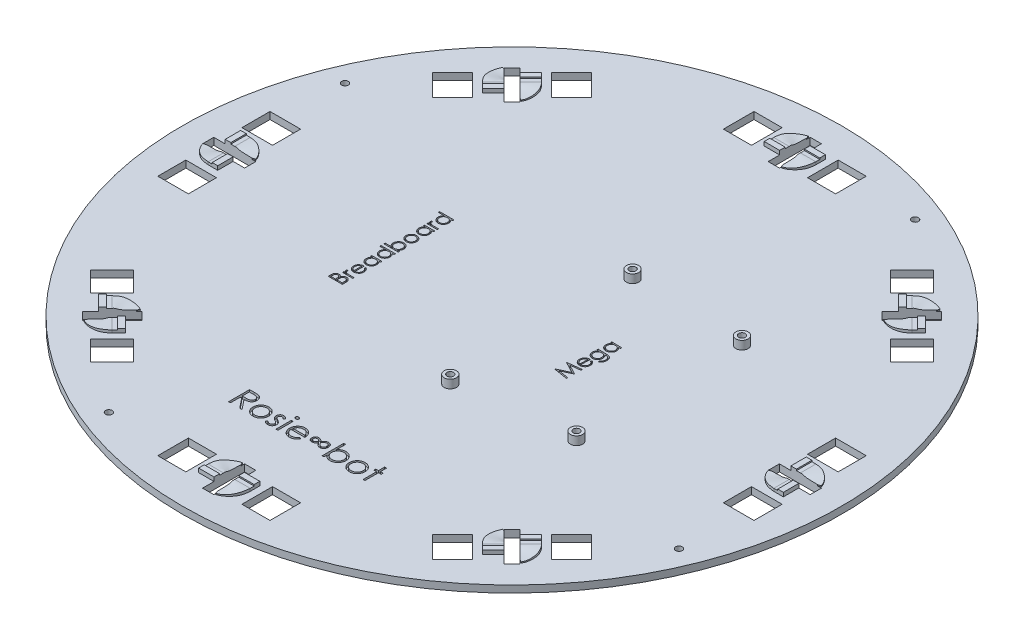
SolidWorks part; units mm, degrees
ref_plane "Front" through (0, 0, 0) normal (0, 0, 1) x (1, 0, 0)
ref_plane "Top" through (0, 0, 0) normal (0, 1, 0) x (1, 0, 0)
ref_plane "Right" through (0, 0, 0) normal (1, 0, 0) x (0, 0, -1)
sketch "Sketch1" plane through (0, 0, 0) normal (0, 1, 0) x (1, 0, 0)
  circle A0 centre (0, 0) radius 149.225
  dimension "D1" = 298.45
extrude "Boss-Extrude1" add sketch "Sketch1" along normal blind 3.175 contours A0
sketch "Sketch2" plane through (0, 3.175, 0) normal (0, 1, 0) x (1, 0, 0)
  line L1 (-2.54, -137.5833) -> (2.54, -137.5833)
  line L2 (-2.54, -137.5833) -> (-2.54, -118.5333)
  line L3 (-2.54, -118.5333) -> (2.54, -118.5333)
  line L4 (2.54, -137.5833) -> (2.54, -118.5333)
  circle A0 centre (0, 0) radius 149.225 construction
  point P4 (0, -118.5333)
  dimension "D1" = 5.08
  dimension "D2" = 19.05
  dimension "D3" = 137.5833
extrude "Cut-Extrude1" cut sketch "Sketch2" against normal up to next and the other way through all contours L1 L4 L3 L2
sketch "Sketch4" plane through (0, 3.175, 0) normal (0, 1, 0) x (1, 0, 0)
  line L0 (0, -128.0583) -> (-2.9434, -118.9995) construction
  line L1 (-2.9434, -118.9995) -> (0, -128.0583) construction
  line L2 (0, -128.0583) -> (-5.5987, -120.3525) construction
  line L3 (0, -128.0583) -> (-7.7059, -122.4597) construction
  line L4 (0, -128.0583) -> (-9.0588, -125.115) construction
  line L5 (0, -128.0583) -> (-9.525, -128.0583) construction
  line L9 (2.54, -118.5333) -> (-2.54, -118.5333) construction
  line L10 (2.54, -118.5333) -> (2.54, -137.5833) construction
  line L11 (-2.54, -118.5333) -> (-2.54, -137.5833) construction
  line L12 (2.54, -137.5833) -> (-2.54, -137.5833) construction
  circle A0 centre (0, -128.0583) radius 9.525 construction
  point P16 (0, -118.5333)
  point P19 (2.54, -128.0583)
  dimension "D1" = 18
  dimension "D2" = 18
  dimension "D3" = 18
  dimension "D4" = 18
  dimension "D5" = 18
ref_plane "Plane1" through (-37.6354, 0, 12.2285) normal (0.9511, 0, -0.309) x (-0.309, 0, -0.9511)
ref_plane "Plane2" through (-60.8954, 0, 44.2431) normal (0.809, 0, -0.5878) x (-0.5878, 0, -0.809)
ref_plane "Plane3" through (-60.8954, 0, 83.8153) normal (0.5878, 0, -0.809) x (-0.809, 0, -0.5878)
ref_plane "Plane4" through (-37.6354, 0, 115.8299) normal (0.309, 0, -0.9511) x (-0.9511, 0, -0.309)
ref_plane "Plane5" through (0, 0, 128.0583) normal (0, 0, -1) x (-1, 0, 0)
sketch "Sketch5" plane through (-37.6354, 0, 12.2285) normal (0.9511, 0, -0.309) x (-0.309, 0, -0.9511)
  line L0 (-111.947, 3.175) -> (-130.0646, 3.175) construction
  line L1 (-113.5711, 3.175) -> (-112.2657, 3.175)
  line L2 (-113.5711, 3.175) -> (-113.5711, 3.683)
  line L3 (-113.5711, 3.683) -> (-112.2657, 3.683)
  line L4 (-112.2657, 3.175) -> (-112.2657, 3.683)
  dimension "D2" = 0.508
sketch "Sketch6" plane through (-60.8954, 0, 44.2431) normal (0.809, 0, -0.5878) x (-0.5878, 0, -0.809)
  line L0 (-94.4025, 3.175) -> (-109.8143, 3.175) construction
  line L1 (-99.2801, 3.175) -> (-94.0764, 3.175)
  line L2 (-99.2801, 3.175) -> (-99.2801, 3.775)
  line L3 (-99.2801, 3.775) -> (-94.0764, 3.775)
  line L4 (-94.0764, 3.175) -> (-94.0764, 3.775)
  dimension "D2" = 0.6
sketch "Sketch7" plane through (-60.8954, 0, 83.8153) normal (0.5878, 0, -0.809) x (-0.809, 0, -0.5878)
  line L0 (-67.6172, 3.175) -> (-78.8146, 3.175) construction
  line L1 (-72.1312, 3.175) -> (-65.7458, 3.175)
  line L2 (-72.1312, 3.175) -> (-72.1312, 4.075)
  line L3 (-72.1312, 4.075) -> (-65.7458, 4.075)
  line L4 (-65.7458, 3.175) -> (-65.7458, 4.075)
  dimension "D2" = 0.9
sketch "Sketch10" plane through (-37.6354, 0, 115.8299) normal (0.309, 0, -0.9511) x (-0.9511, 0, -0.309)
  line L0 (-39.5722, 3.175) -> (-30.5134, 3.175) construction
  line L1 (-36.9015, 3.175) -> (-30.0472, 3.175)
  line L2 (-36.9015, 3.175) -> (-36.9015, 4.375)
  line L3 (-36.9015, 4.375) -> (-30.0472, 4.375)
  line L4 (-30.0472, 3.175) -> (-30.0472, 4.375)
  dimension "D3" = 1.2
sketch "Sketch11" plane through (0, 0, 128.0583) normal (0, 0, -1) x (-1, 0, 0)
  line L0 (0, 3.175) -> (9.525, 3.175) construction
  line L1 (2.54, 3.175) -> (9.525, 3.175)
  line L2 (2.54, 3.175) -> (2.54, 4.375)
  line L3 (2.54, 4.375) -> (9.525, 4.375)
  line L4 (9.525, 3.175) -> (9.525, 4.375)
  dimension "D3" = 1.2
loft "Loft1" add profiles "Sketch5", "Sketch6", "Sketch7", "Sketch10", "Sketch11" connector at (-2.54, 3.683, 120.241) connector at (-2.54, 3.775, 124.5623) connector at (-2.54, 4.075, 126.2129) connector at (-2.54, 4.375, 127.233) connector at (-2.54, 4.375, 128.0583)
sketch "Sketch13" plane through (-104.9799, 0, 128.0583) normal (0, 0, -1) x (-1, 0, 0)
  line L6 (-95.4549, 3.175) -> (-102.4399, 3.175)
  line L7 (-95.4549, 3.175) -> (-95.4549, 4.375)
  line L8 (-95.4549, 4.375) -> (-102.4399, 4.375)
  line L9 (-102.4399, 3.175) -> (-102.4399, 4.375)
extrude "Boss-Extrude4" add sketch "Sketch13" against normal blind 1.7907
sketch "Sketch25" plane through (0, 0, 129.849) normal (0, 0, 1) x (1, 0, 0)
  line L0 (-9.525, 4.375) -> (-2.54, 4.375) construction
  line L1 (-9.525, 3.175) -> (-2.54, 3.175)
  line L2 (-9.525, 3.175) -> (-9.525, 4.975)
  line L3 (-9.525, 4.975) -> (-2.54, 4.975)
  line L4 (-2.54, 3.175) -> (-2.54, 4.975)
  dimension "D1" = 0.6
extrude "Boss-Extrude5" add sketch "Sketch25" along normal blind 2.54
sketch "Sketch14" plane through (-2.54, 0, 0) normal (1, 0, 0) x (0, 0, -1)
  line L0 (-128.0583, 3.175) -> (-128.0583, 0) construction
  line L1 (-118.5333, 0) -> (-137.5833, 0) construction
ref_plane "Plane6" through (0, 0, 0) normal (1, 0, 0) x (0, 0, -1)
sketch "Sketch15" plane through (0, 0, 0) normal (1, 0, 0) x (0, 0, -1)
  line L0 (-128.0583, 0) -> (-128.0583, 3.175) construction
pattern_circular "CirPattern1" count 2 over 360 about axis through (0, 0, 128.0583) along (0, 1, 0) of "Loft1", "Boss-Extrude5", "Boss-Extrude4" reverse direction yes
ref_axis "Axis1" through (0, 50, 0) along (0, -1, 0)
pattern_circular "CirPattern5" count 8 over 360 about axis through (0, 50, 0) along (0, -1, 0) of "CirPattern1", "Cut-Extrude1"
sketch "Sketch18" plane through (0, 3.175, 0) normal (0, 1, 0) x (1, 0, 0)
  line L0 (12.7, 40.64) -> (63.5, 40.64) construction
  line L1 (12.7, 40.64) -> (12.7, -40.64) construction
  line L2 (63.5, -34.29) -> (12.7, -34.29) construction
  line L3 (63.5, -34.29) -> (63.5, 40.64) construction
  line L4 (0, -149.225) -> (0, 149.225) construction
  line L5 (0, -1.7463) -> (0, 1.7463) construction
  line L6 (-149.225, 0) -> (149.225, 0) construction
  line L7 (12.7, 41.91) -> (12.7, 40.64) construction
  circle A0 centre (12.7, 41.91) radius 2.77
  circle A1 centre (12.7, -40.64) radius 2.77
  circle A2 centre (63.5, -34.29) radius 2.77
  circle A3 centre (63.5, 40.64) radius 2.77
  circle A4 centre (12.7, -40.64) radius 1.5
  circle A5 centre (12.7, 41.91) radius 1.5
  circle A6 centre (63.5, 40.64) radius 1.5
  circle A7 centre (63.5, -34.29) radius 1.5
  circle A8 centre (0, 0) radius 149.225 construction
  point P22 (12.7, 0)
  dimension "D7" = 12.7
  dimension "D5" = 3
  dimension "D6" = 1.27
  dimension "D1" = 82.55
  dimension "D2" = 74.93
  dimension "D3" = 50.8
  dimension "D4" = 1.27
sketch "Sketch19" plane through (0, 3.175, 0) normal (0, 1, 0) x (1, 0, 0)
  line L0 (-53.4609, -129.066) -> (0, 0) construction
  line L1 (0, -149.225) -> (0, 149.225) construction
  circle A1 centre (-53.4609, -129.066) radius 1.5
  dimension "D1" = 139.7
  dimension "D4" = 3
  dimension "D5" = 22.5
extrude "Cut-Extrude2" cut sketch "Sketch19" against normal through all
pattern_circular "CirPattern7" count 4 over 360 about axis through (0, 50, 0) along (0, -1, 0) of "Cut-Extrude2"
extrude "Boss-Extrude3" add sketch "Sketch18" along normal blind 3.81
sketch "Sketch23" plane through (0, 3.175, 0) normal (0, 1, 0) x (1, 0, 0)
  line L9 (-2.54, -132.389) -> (-2.54, -137.5833) construction
  line L10 (-25.4, -121.1305) -> (-12.7, -121.1305)
  line L11 (-25.4, -121.1305) -> (-25.4, -134.9862)
  line L16 (-25.4, -134.9862) -> (-12.7, -134.9862)
  line L17 (-12.7, -121.1305) -> (-12.7, -134.9862)
  line L19 (2.54, -118.5333) -> (2.54, -123.7276) construction
  line L20 (0, -50) -> (0, 50) construction
  line L21 (12.7, -121.1305) -> (12.7, -134.9862)
  line L22 (25.4, -134.9862) -> (12.7, -134.9862)
  line L23 (25.4, -121.1305) -> (25.4, -134.9862)
  line L24 (25.4, -121.1305) -> (12.7, -121.1305)
  point P8 (-2.54, -134.9862)
  point P9 (2.54, -121.1305)
  dimension "D1" = 12.7
  dimension "D2" = 10.16
extrude "Cut-Extrude6" cut sketch "Sketch23" against normal through all
sketch "Sketch17" plane through (0, 3.175, 0) normal (0, 1, 0) x (1, 0, 0)
  line L0 (-31.75, -97.8162) -> (31.75, -97.8162) construction
  point P3 (0, -97.8162)
  dimension "D2" = 97.8162
  dimension "D1" = 63.5
pattern_circular "CirPattern8" count 8 over 360 about axis through (0, 50, 0) along (0, -1, 0) of "Cut-Extrude6"
sketch "Sketch16" plane through (0, 3.175, 0) normal (0, 1, 0) x (1, 0, 0)
  line L0 (-31.75, -97.8162) -> (31.75, -97.8162) construction
  text T0 "Rosie∞bot\r\n" font "Century Gothic" height in points 36
extrude "Cut-Extrude4" cut sketch "Sketch16" against normal blind 1.27
sketch "Sketch22" plane through (0, 3.175, 0) normal (0, 1, 0) x (1, 0, 0)
  line L0 (-50.8, 25.1735) -> (-50.8, -31.2294) construction
  text T0 "Breadboard"
  dimension "D1" = 50.8
extrude "Cut-Extrude5" cut sketch "Sketch22" against normal blind 1.27
sketch "Sketch24" plane through (0, 3.175, 0) normal (0, 1, 0) x (1, 0, 0)
  line L0 (36.7515, -12.6663) -> (37.3848, 12.6663) construction
  circle A0 centre (12.7, 41.91) radius 1.5 construction
  circle A1 centre (63.5, 40.64) radius 1.5 construction
  text T0 "Mega"
  point P12 (37.0681, 0)
extrude "Cut-Extrude7" cut sketch "Sketch24" against normal blind 1.27
